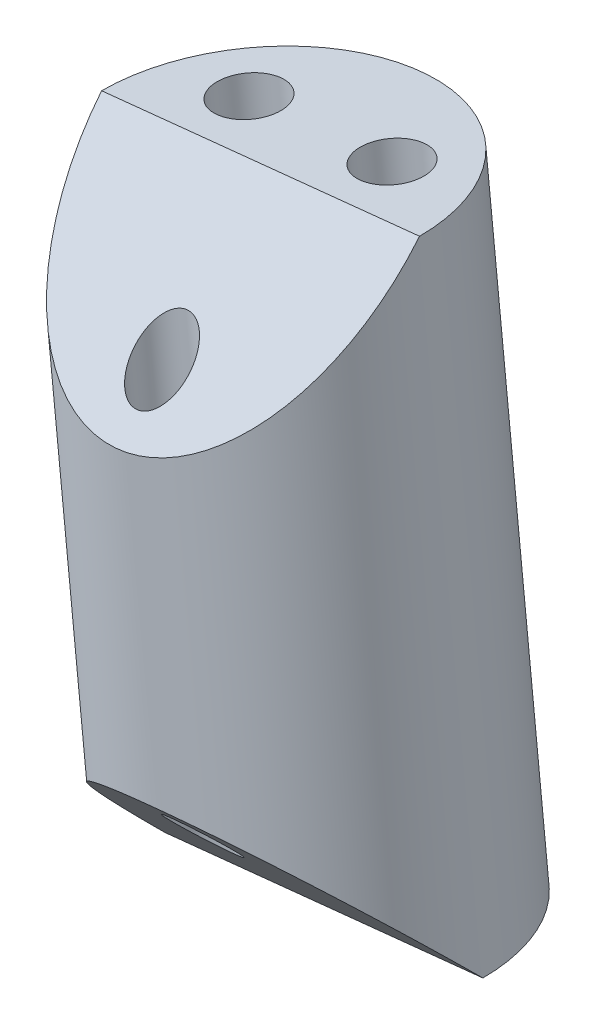
SolidWorks part; units mm, degrees
ref_plane "Front Plane" through (0, 0, 0) normal (0, 0, 1) x (1, 0, 0)
ref_plane "Top Plane" through (0, 0, 0) normal (0, 1, 0) x (1, 0, 0)
ref_plane "Right Plane" through (0, 0, 0) normal (1, 0, 0) x (0, 0, -1)
sketch "Sketch2" plane through (0, 0, 0) normal (0, 0, 1) x (1, 0, 0)
  line L0 (0, 0) -> (90, 0)
  line L1 (90, 0) -> (90, 120)
  line L2 (90, 120) -> (0, 120)
  line L3 (0, 120) -> (0, 0)
  line L4 (0, 120) -> (-10, 120)
  line L5 (-10, 120) -> (-10, 16.9491)
  line L6 (-10, 120) -> (57.5, 127)
  line L7 (57.5, 127) -> (90, 124)
  line L8 (90, 120) -> (99, 60)
  line L10 (90, 124) -> (90, 120)
  line L11 (5.9147, 0) -> (5.9147, -25)
  line L12 (5.9147, -25) -> (-4.0853, -25)
  line L13 (-4.0853, -29) -> (-4.0853, 0)
  line L14 (80, 0) -> (80, -25)
  line L15 (80, -25) -> (90, -25)
  line L16 (90, -29) -> (90, 0)
  line L17 (15.7927, 122.6748) -> (5.4776, 222.1414)
  line L18 (5.4776, 222.1414) -> (21.3923, 223.7918)
  line L19 (21.3923, 223.7918) -> (31.7073, 124.3252)
  line L20 (7.6492, 201.201) -> (23.5639, 202.8514)
  line L21 (10.9066, 169.7905) -> (26.8212, 171.441)
  line L22 (-10, 120) -> (-20.0396, 216.8108)
  line L23 (-20.0396, 216.8108) -> (-4.125, 218.4612)
  line L24 (-4.125, 218.4612) -> (5.9147, 121.6504)
  line L25 (-17.926, 196.4296) -> (-2.0114, 198.08)
  line L26 (-14.7556, 165.8578) -> (1.159, 167.5082)
  line L27 (57.5, 127) -> (46.9095, 229.1223)
  line L28 (46.9095, 229.1223) -> (30.9949, 227.4719)
  line L29 (30.9949, 227.4719) -> (41.5853, 125.3496)
  line L30 (33.2245, 205.9725) -> (49.1391, 207.6229)
  line L31 (36.5688, 173.7233) -> (52.4835, 175.3737)
  line L34 (90, 124) -> (99.1917, 223.5767)
  line L35 (99.1917, 223.5767) -> (83.2594, 225.0473)
  line L36 (83.2594, 225.0473) -> (74.0677, 125.4707)
  line L38 (81.3243, 204.0838) -> (97.2566, 202.6132)
  line L39 (78.4217, 172.6386) -> (94.354, 171.1679)
  line L40 (62.4078, 79.6749) -> (57.5, 127) construction
  line L41 (41.5853, 125.3496) -> (46.4931, 78.0244) construction
  line L42 (46.4931, 78.0244) -> (62.4078, 79.6749) construction
  line L43 (31.7073, 124.3252) -> (36.6151, 77.0001) construction
  line L44 (36.6151, 77.0001) -> (20.7005, 75.3496) construction
  line L45 (20.7005, 75.3496) -> (15.7927, 122.6748) construction
  line L46 (5.9147, 121.6504) -> (10.8224, 74.3253) construction
  line L47 (10.8224, 74.3253) -> (-5.0922, 72.6749) construction
  line L48 (-5.0922, 72.6749) -> (-10, 120) construction
  line L49 (74.0677, 125.4707) -> (69.6944, 78.0931) construction
  line L50 (69.6944, 78.0931) -> (85.7624, 78.0931) construction
  line L51 (85.7624, 78.0931) -> (90, 124) construction
  line L52 (-12.0823, 217.636) -> (10.4873, 0) construction
  line L53 (13.4349, 222.9666) -> (36.5574, 0) construction
  line L54 (38.9522, 228.2971) -> (62.6275, 0) construction
  line L55 (91.2256, 224.312) -> (70.5198, 0) construction
  line L59 (99, 60) -> (93.5277, 44.9649)
  line L60 (99, 60) -> (169.4769, 34.3485)
  line L61 (169.4769, 34.3485) -> (164.0046, 19.3134)
  line L62 (164.0046, 19.3134) -> (93.5277, 44.9649)
  line L63 (90, -2) -> (100, -2)
  line L64 (141.2862, 44.6091) -> (135.8138, 29.574)
  line L65 (99, 60) -> (55.7741, 75.7329) construction
  line L66 (55.7741, 75.7329) -> (50.3018, 60.6978) construction
  line L67 (100, -2) -> (100, -29)
  line L70 (-4.0853, -2) -> (-14.0853, -2)
  line L71 (-14.0853, -2) -> (-14.0853, -29)
  line L74 (-4.0853, 0) -> (0, 0)
  line L75 (-14.0853, -29) -> (-14.0853, -112.587)
  line L76 (-14.0853, -112.587) -> (100, -112.587)
  line L77 (100, -112.587) -> (100, -29)
  line L78 (-14.0853, -29) -> (100, -29)
  line L79 (-14.0853, -14.5) -> (100, -14.5) construction
  line L80 (31.7073, -112.587) -> (31.7073, -122.6232)
  line L81 (31.7073, -122.6232) -> (42.9573, -122.6232)
  line L82 (42.9573, -122.6232) -> (42.9573, -112.587)
  line L83 (-14.0853, -112.587) -> (-88.3667, -112.587)
  line L84 (-88.3667, -112.587) -> (-88.3667, -128.2699)
  line L85 (-88.3667, -128.2699) -> (169.4958, -128.2699)
  line L86 (169.4958, -128.2699) -> (169.4958, -112.587)
  line L87 (169.4958, -112.587) -> (100, -112.587)
  line L88 (90, 60) -> (-10, 60) construction
  line L89 (50.3018, 60.6978) -> (93.5277, 44.9649) construction
  line L90 (87.2806, 55.7521) -> (166.7408, 26.8309) construction
  line L91 (87.2806, 55.7521) -> (82.1749, 52.5336) construction
  line L92 (82.1749, 52.5336) -> (77.3257, 0) construction
  line L93 (83.1185, 56.6957) -> (86.337, 51.59) construction
  arc A0 (-10, 16.9491) -> (-4.0853, 0) centre (14.9876, 16.1624) ccw
  arc A1 (93.5277, 44.9649) -> (90, 0) centre (-126.4069, 39.5988) cw
  point P42 (41.1818, 206.7977)
  point P100 (84.7278, 54.1428)
  point P101 (84.7278, 54.1428)
  dimension "D11" = 47.3684
  dimension "D35" = 9
  dimension "D32" = 220
  dimension "D36" = 25
  dimension "D1" = 120
  dimension "D2" = 90
  dimension "D3" = 10
  dimension "D5" = 67.862
  dimension "D6" = 7
  dimension "D7" = 4
  dimension "D8" = 16
  dimension "D9" = 16
  dimension "D10" = 100
  dimension "D12" = 31.5789
  dimension "D13" = 16
  dimension "D14" = 16
  dimension "D15" = 16
  dimension "D16" = 25.7927
  dimension "D17" = 100
  dimension "D18" = 21.0526
  dimension "D19" = 31.5789
  dimension "D20" = 97.33
  dimension "D21" = 102.67
  dimension "D22" = 20.4905
  dimension "D23" = 30.7358
  dimension "D24" = 21.6147
  dimension "D25" = 32.4221
  dimension "D26" = 25
  dimension "D28" = 25
  dimension "D29" = 75
  dimension "D30" = 47.5789
  dimension "D31" = 30
  dimension "D33" = 46
  dimension "D34" = 20
  dimension "D37" = 2
  dimension "D38" = 2
  dimension "D39" = 27
  dimension "D40" = 10
  dimension "D41" = 10
  dimension "D42" = 27
  dimension "D43" = 14.5
  dimension "D44" = 127.5
ref_plane "Plane1" through (87.2806, 55.7521, 0) normal (-0.846, -0.5333, 0) x (0, 0, 1)
ref_plane "Plane2" through (82.1749, 52.5336, 0) normal (-0.0919, -0.9958, 0) x (-0.9958, 0.0919, 0)
ref_plane "Plane3" through (91.2256, 224.312, 0) normal (-0.0919, -0.9958, 0) x (-0.9958, 0.0919, 0)
ref_plane "Plane4" through (38.9522, 228.2971, 0) normal (0.1032, -0.9947, 0) x (-0.9947, -0.1032, 0)
ref_plane "Plane5" through (13.4349, 222.9666, 0) normal (0.1032, -0.9947, 0) x (-0.9947, -0.1032, 0)
ref_plane "Plane7" through (166.7408, 26.8309, 0) normal (0.9397, -0.342, 0) x (0, 0, -1)
ref_plane "Plane8" through (110.4217, -40.1902, 0) normal (0.9397, -0.342, 0) x (0, 0, -1)
ref_plane "Plane9" through (19.3664, 209.803, 0) normal (-0.0919, -0.9958, 0) x (-0.9958, 0.0919, 0)
ref_plane "Plane10" through (16.4638, 178.3578, 0) normal (-0.0919, -0.9958, 0) x (-0.9958, 0.0919, 0)
ref_plane "Plane11" through (-20.7793, 200.3721, 0) normal (0.1032, -0.9947, 0) x (-0.9947, -0.1032, 0)
ref_plane "Plane12" through (-17.435, 168.1229, 0) normal (0.1032, -0.9947, 0) x (-0.9947, -0.1032, 0)
ref_plane "Plane13" through (-20.5619, 198.2754, 0) normal (0.1032, -0.9947, 0) x (-0.9947, -0.1032, 0)
ref_plane "Plane14" through (-17.3045, 166.8649, 0) normal (0.1032, -0.9947, 0) x (-0.9947, -0.1032, 0)
ref_plane "Plane15" through (-12.0823, 217.636, 0) normal (0.1032, -0.9947, 0) x (-0.9947, -0.1032, 0)
ref_plane "Plane16" through (-20.3445, 196.1788, 0) normal (0.1032, -0.9947, 0) x (-0.9947, -0.1032, 0)
ref_plane "Plane17" through (-17.1741, 165.607, 0) normal (0.1032, -0.9947, 0) x (-0.9947, -0.1032, 0)
ref_plane "Plane18" through (12.1098, 131.1899, 0) normal (-0.0919, -0.9958, 0) x (-0.9958, 0.0919, 0)
ref_plane "Plane19" through (-12.4184, 119.7492, 0) normal (0.1032, -0.9947, 0) x (-0.9947, -0.1032, 0)
ref_plane "Plane20" through (0, 0, 0) normal (0, 0, 1) x (0.1032, -0.9947, 0)
ref_plane "Plane21" through (0, 0, 0) normal (0, 0, 1) x (-0.0919, -0.9958, 0)
ref_plane "Plane22" through (10.3758, 1.076, 0) normal (-0.9947, -0.1032, 0) x (0.1032, -0.9947, 0)
ref_plane "Plane23" through (36.1684, 3.7508, 0) normal (-0.9947, -0.1032, 0) x (0.1032, -0.9947, 0)
ref_plane "Plane24" through (61.9611, 6.4256, 0) normal (-0.9947, -0.1032, 0) x (0.1032, -0.9947, 0)
ref_plane "Plane25" through (69.924, -6.4545, 0) normal (-0.9958, 0.0919, 0) x (-0.0919, -0.9958, 0)
sketch "Sketch3" plane through (-20.3445, 196.1788, 0) normal (0.1032, -0.9947, 0) x (-0.9947, -0.1032, 0)
  line L0 (-2.4314, 0) -> (-18.4314, 0) construction
  circle A0 centre (-10.4314, 0) radius 8
  dimension "D1" = 16
extrude "Boss-Extrude1" add sketch "Sketch3" along normal blind 30.7358
sketch "Sketch4" plane through (10.3758, 1.076, 0) normal (-0.9947, -0.1032, 0) x (0.1032, -0.9947, 0)
  line L0 (-197.2309, 0) -> (-189.2309, 8)
  line L1 (-197.2309, 8) -> (-197.2309, -8) construction
  line L2 (-166.4951, 8) -> (-197.2309, 8) construction
  line L3 (-189.2309, 8) -> (-197.2309, 8)
  line L4 (-197.2309, 8) -> (-197.2309, 0)
  line L5 (-174.4951, 8) -> (-166.4951, 8)
  line L6 (-166.4951, 8) -> (-166.4951, 0)
  line L7 (-217.7214, 0) -> (1.0818, 0) construction
  line L8 (-166.4951, 0) -> (-174.4951, 8)
  dimension "D1" = 45
  dimension "D2" = 45
extrude "Cut-Extrude1" cut sketch "Sketch4" against normal through all and the other way through all
sketch "Sketch5" plane through (10.3758, 1.076, 0) normal (-0.9947, -0.1032, 0) x (0.1032, -0.9947, 0)
  line L0 (-166.4951, 0) -> (-170.4951, 4)
  line L1 (-166.4951, 0) -> (-174.4951, 8) construction
  line L2 (-170.4951, 4) -> (-162.4951, 4)
  line L3 (-162.4951, 4) -> (-162.4951, 0)
  line L4 (-213.7055, 0) -> (7.2742, 0) construction
  line L6 (-166.4951, 0) -> (-162.4951, 4) construction
  line L7 (-162.4951, 0) -> (-166.4951, -4)
  line L8 (-166.4951, -8) -> (-166.4951, 0) construction
  line L9 (-166.4951, 0) -> (-166.4951, -4)
  dimension "D1" = 4
  dimension "D2" = 45
sketch "Sketch7" plane through (10.3758, 1.076, 0) normal (-0.9947, -0.1032, 0) x (0.1032, -0.9947, 0)
  line L0 (-193.2309, 4) -> (-197.2309, 0)
  line L1 (-217.7214, 0) -> (1.0818, 0) construction
  line L4 (-197.2309, -4) -> (-197.2309, 0)
  line L5 (-193.2309, 4) -> (-193.2309, 0)
  arc A0 (-197.2309, -4) -> (-193.2309, 0) centre (-197.2309, 0) ccw
  dimension "D1" = 4
  dimension "D2" = 4
sketch "Sketch8" plane through (-20.3445, 196.1788, 0) normal (-0.1032, 0.9947, 0) x (0.9947, 0.1032, 0)
  line L0 (2.4314, 0) -> (18.4314, 0) construction
  circle A0 centre (10.4314, -5.5) radius 1.4
  circle A1 centre (6.8314, 3) radius 1.6
  circle A2 centre (14.0314, 3) radius 1.6
  point P9 (10.4314, 0)
  dimension "D1" = 3.2
  dimension "D2" = 3.2
  dimension "D3" = 2.8
  dimension "D4" = 3
  dimension "D5" = 5.5
  dimension "D6" = 3.6
  dimension "D7" = 3.6
  dimension "D8" = 3
extrude "Cut-Extrude3" cut sketch "Sketch8" against normal through all and the other way through all
sketch "Sketch9" plane through (-20.3445, 196.1788, 0) normal (-0.1032, 0.9947, 0) x (0.9947, 0.1032, 0)
  line L0 (4.5289, 5.4) -> (16.3339, 5.4)
  line L1 (-101.1265, 0) -> (155.3606, 0) construction
  arc A0 (18.4314, 0) -> (2.4314, 0) centre (10.4314, 0) ccw construction
  arc A1 (4.5289, 5.4) -> (16.3339, 5.4) centre (10.4314, 0) cw
  dimension "D1" = 5.4
